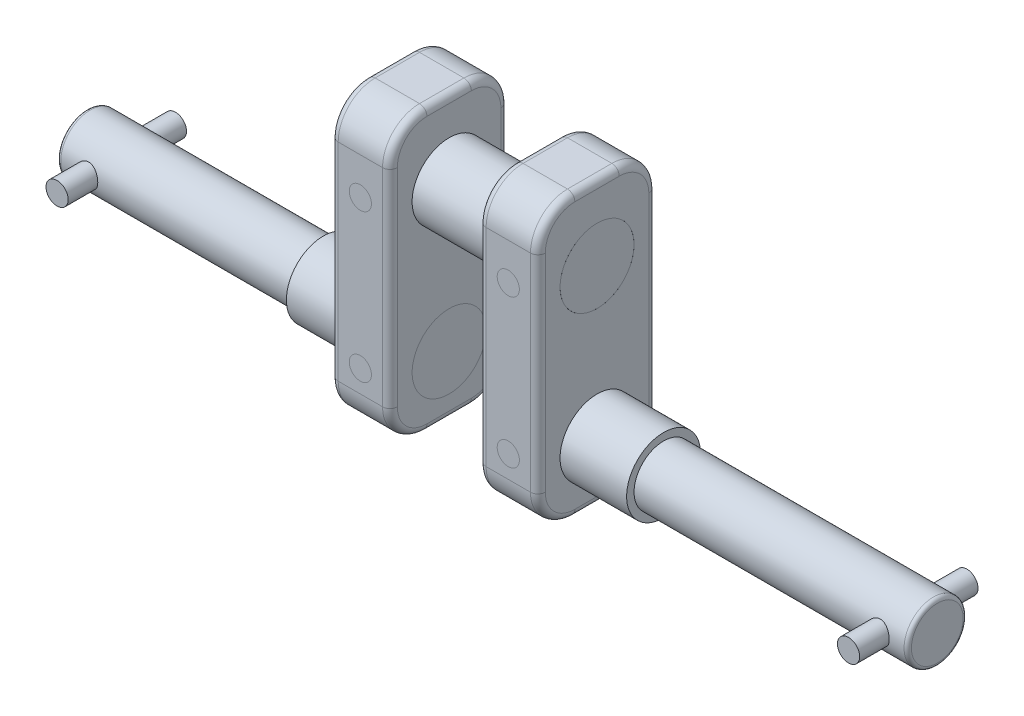
SolidWorks part; units mm, degrees
ref_plane "Front Plane" through (0, 0, 0) normal (0, 0, 1) x (1, 0, 0)
ref_plane "Top Plane" through (0, 0, 0) normal (0, 1, 0) x (1, 0, 0)
ref_plane "Right Plane" through (0, 0, 0) normal (1, 0, 0) x (0, 0, -1)
sketch "Sketch1" plane through (0, 0, 0) normal (1, 0, 0) x (0, 0, -1)
  circle A0 centre (0, 0) radius 4
  dimension "D1" = 8
extrude "Boss-Extrude1" add sketch "Sketch1" along normal blind 32
sketch "Sketch2" plane through (32, 0, 0) normal (1, 0, 0) x (0, 0, -1)
  circle A0 centre (0, 0) radius 5
  dimension "D1" = 10
extrude "Boss-Extrude2" add sketch "Sketch2" along normal blind 17 separate body
sketch "Sketch3" plane through (49, 0, 0) normal (1, 0, 0) x (0, 0, -1)
  line L0 (0, 34.8851) -> (0, -34.8851) construction
  line L1 (-3, -8) -> (3, -8)
  line L2 (-8, -3) -> (-8, 25)
  line L3 (-3, 30) -> (3, 30)
  line L4 (8, -3) -> (8, 25)
  circle A0 centre (0, 0) radius 5 construction
  circle A1 centre (0, 0) radius 5
  circle A2 centre (0, 20) radius 5
  arc A3 (3, -8) -> (8, -3) centre (3, -3) ccw
  arc A4 (-3, -8) -> (-8, -3) centre (-3, -3) cw
  arc A5 (3, 30) -> (8, 25) centre (3, 25) cw
  arc A6 (-8, 25) -> (-3, 30) centre (-3, 25) cw
  point P9 (0, 0)
  point P19 (8, 30)
  point P22 (-8, 30)
  dimension "D5" = 5
  dimension "D1" = 20
  dimension "D2" = 8
  dimension "D3" = 10
  dimension "D4" = 16
extrude "Boss-Extrude3" add sketch "Sketch3" against normal blind 8 separate body
sketch "Sketch4" plane through (41, 0, 0) normal (-1, 0, 0) x (0, 0, 1)
  circle A0 centre (0, 20) radius 5 construction
  circle A1 centre (0, 20) radius 5
extrude "Boss-Extrude4" add sketch "Sketch4" against normal blind 28 separate body
ref_plane "Plane1" through (55, 0, 0) normal (-1, 0, 0) x (0, 0, 1)
mirror "Mirror1" about plane through (55, 0, 0) normal (-1, 0, 0) of bodies 103 102
sketch "Sketch5" plane through (78, 0, 0) normal (1, 0, 0) x (0, 0, -1)
  circle A0 centre (0, 0) radius 4
  point P3 (0, 0)
  dimension "D1" = 8
extrude "Boss-Extrude5" add sketch "Sketch5" along normal blind 37
sketch "Sketch6" plane through (0, 0, 8) normal (0, 0, 1) x (1, 0, 0)
  line L0 (41, 25) -> (41, -3) construction
  line L1 (69, 25) -> (69, -3) construction
  line L2 (41, 30) -> (49, 30) construction
  line L4 (115, -4) -> (115, 4) construction
  circle A0 centre (4, 0) radius 1.5
  circle A1 centre (45, 0) radius 1.5
  circle A2 centre (65, 0) radius 1.5
  circle A3 centre (111, 0) radius 1.5
  circle A4 centre (65, 20) radius 1.5
  circle A5 centre (45, 20) radius 1.5
  point P12 (0, 0)
  point P13 (0, 0)
  point P14 (0, 0)
  point P15 (0, 0)
  point P16 (0, 0)
  point P19 (0, 0)
  point P24 (0, 0)
  point P25 (0, 0)
  point P29 (0, 0)
  point P30 (0, 0)
  dimension "D5" = 3
  dimension "D1" = 4
  dimension "D2" = 4
  dimension "D3" = 10
  dimension "D4" = 20
  dimension "D6" = 4
  dimension "D7" = 4
extrude "Cut-Extrude1" cut sketch "Sketch6" against normal through all
extrude "Boss-Extrude6" add sketch "Sketch6<2>" against normal blind 16 separate body
sketch "Sketch6<2>" plane through (0, 0, 8) normal (0, 0, 1) x (1, 0, 0) same geometry as "Sketch6"
fillet "Fillet1" radius 1 16 edges at (41, -6.5355, -6.5355) (41, -8, 0) (41, -6.5355, 6.5355) (41, 11, 8) (41, 28.5355, 6.5355) (41, 30, 0) (41, 28.5355, -6.5355) (49, 28.5355, 6.5355) (49, 30, 0) (49, 28.5355, -6.5355) (49, 11, -8) (49, -6.5355, -6.5355) (49, -8, 0) (49, -6.5355, 6.5355) (41, 11, -8) (49, 11, 8)
fillet "Fillet2" radius 1 16 edges at (69, -6.5355, -6.5355) (69, -8, 0) (69, -6.5355, 6.5355) (69, 11, 8) (69, 28.5355, 6.5355) (69, 30, 0) (69, 28.5355, -6.5355) (61, -6.5355, -6.5355) (61, -8, 0) (61, -6.5355, 6.5355) (61, 11, 8) (61, 28.5355, 6.5355) (61, 30, 0) (61, 28.5355, -6.5355) (69, 11, -8) (61, 11, -8)
fillet "Fillet3" radius 0.5 1 edges at (0, 0, -4)
fillet "Fillet4" radius 0.5 1 edges at (115, 0, -4)
